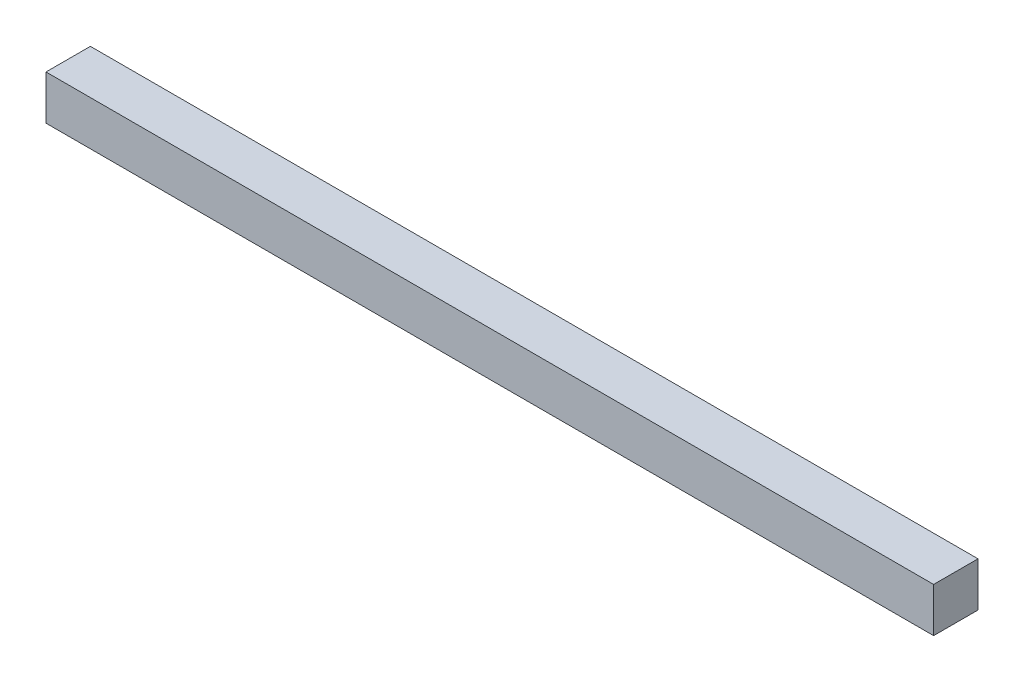
SolidWorks part; units mm, degrees
material "Plain Carbon Steel"
ref_plane "Front Plane" through (0, 0, 0) normal (0, 0, 1) x (1, 0, 0)
ref_plane "Top Plane" through (0, 0, 0) normal (0, 1, 0) x (1, 0, 0)
ref_plane "Right Plane" through (0, 0, 0) normal (1, 0, 0) x (0, 0, -1)
sketch "Sketch1" plane through (0, 0, 0) normal (0, 0, 1) x (1, 0, 0)
  line L0 (-100, -5) -> (100, -5)
  line L1 (100, -5) -> (100, 5)
  line L2 (100, 5) -> (-100, 5)
  line L3 (-100, 5) -> (-100, -5)
extrude "Boss-Extrude1" add sketch "Sketch1" along normal mid plane 10
